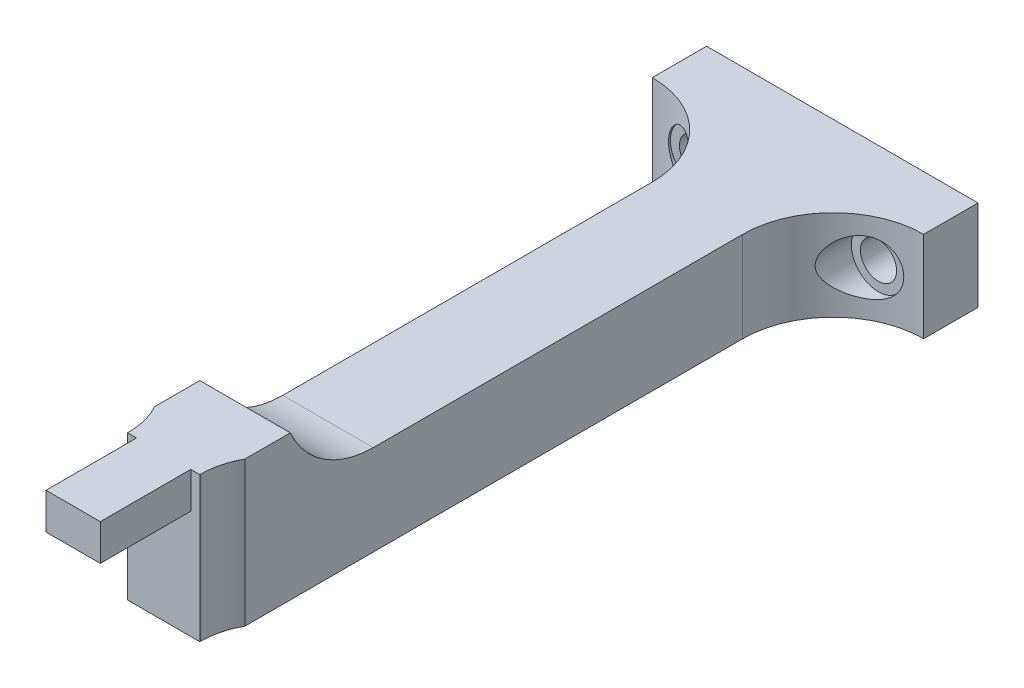
SolidWorks part; units mm, degrees
ref_plane "Front Plane" through (0, 0, 0) normal (0, 0, 1) x (1, 0, 0)
ref_plane "Top Plane" through (0, 0, 0) normal (0, 1, 0) x (1, 0, 0)
ref_plane "Right Plane" through (0, 0, 0) normal (1, 0, 0) x (0, 0, -1)
sketch "Sketch1" plane through (0, 0, 0) normal (0, 0, 1) x (1, 0, 0)
  line L1 (-5, 5) -> (5, 5)
  line L2 (-5, 5) -> (-5, -5)
  line L3 (-5, -5) -> (5, -5)
  line L4 (5, 5) -> (5, -5)
  line L5 (-5, 5) -> (5, -5) construction
  line L6 (-5, -5) -> (5, 5) construction
  point P0 (0, 0)
  dimension "D1" = 10
  dimension "D2" = 10
extrude "Boss-Extrude1" add sketch "Sketch1" along normal blind 65
sketch "Sketch2" plane through (0, 0, 0) normal (0, 0, -1) x (-1, 0, 0)
  line L0 (-5, 5) -> (5, 5) construction
  line L1 (-15, -5) -> (15, -5)
  line L2 (-15, -5) -> (-15, 5)
  line L3 (-15, 5) -> (15, 5)
  line L4 (15, -5) -> (15, 5)
  line L5 (-15, -5) -> (15, 5) construction
  line L6 (-15, 5) -> (15, -5) construction
  line L7 (-5, -5) -> (-5, 5) construction
  line L8 (-15, 5) -> (-5, -5) construction
  line L10 (5, 5) -> (15, -5) construction
  circle A0 centre (-10, 0) radius 2
  circle A1 centre (10, 0) radius 2
  point P0 (0, 0)
  dimension "D1" = 10
extrude "Boss-Extrude2" add sketch "Sketch2" along normal blind 6 contours L2 L3 L4 L1 | A0 | A1
sketch "Sketch3" plane through (0, 5, 0) normal (0, 1, 0) x (1, 0, 0)
  line L1 (-5, -65) -> (5, -65)
  line L2 (-5, -65) -> (-5, -60)
  line L3 (-5, -60) -> (5, -60)
  line L4 (5, -65) -> (5, -60)
  dimension "D1" = 5
extrude "Boss-Extrude3" add sketch "Sketch3" along normal blind 6
sketch "Sketch4" plane through (0, 0, 65) normal (0, 0, 1) x (1, 0, 0)
  line L0 (-5, 11) -> (5, 11) construction
  line L1 (-4, -5) -> (4, -5)
  line L2 (-4, -5) -> (-4, 11)
  line L3 (-4, 11) -> (4, 11)
  line L4 (4, -5) -> (4, 11)
  line L5 (-5, -5) -> (5, -5) construction
  point P6 (0, -5)
  dimension "D1" = 8
extrude "Boss-Extrude4" add sketch "Sketch4" along normal blind 4
sketch "Sketch5" plane through (0, 0, 69) normal (0, 0, 1) x (1, 0, 0)
  line L1 (-3, 7) -> (3, 7)
  line L2 (-3, 7) -> (-3, 11)
  line L3 (-3, 11) -> (3, 11)
  line L4 (3, 7) -> (3, 11)
  line L5 (4, 11) -> (-4, 11) construction
  point P4 (0, 11)
  dimension "D1" = 6
  dimension "D2" = 4
extrude "Boss-Extrude5" add sketch "Sketch5" along normal blind 10
fillet "Fillet1" radius 10 3 edges at (-5, 0, 0) (5, 0, 0) (0, 5, 60)
sketch "Sketch6" plane through (0, 0, 69) normal (0, 0, 1) x (1, 0, 0)
  line L0 (-10, 0) -> (10, 0) construction
  circle A0 centre (-10, 0) radius 3
  circle A1 centre (10, 0) radius 3
extrude "Cut-Extrude1" cut sketch "Sketch6" against normal offset from surface (69 mm away) 6 up to face at (8, 0, -6)
fillet "Fillet2" radius 8 2 edges at (4, 3, 65) (-4, 3, 65)
